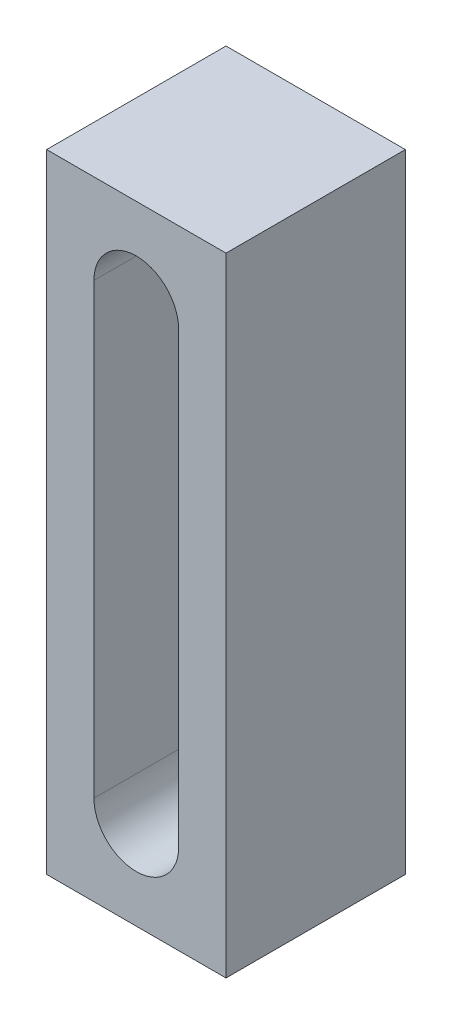
SolidWorks part; units mm, degrees
ref_plane "Front Plane" through (0, 0, 0) normal (0, 0, 1) x (1, 0, 0)
ref_plane "Top Plane" through (0, 0, 0) normal (0, 1, 0) x (1, 0, 0)
ref_plane "Right Plane" through (0, 0, 0) normal (1, 0, 0) x (0, 0, -1)
sketch "Sketch1" plane through (0, 0, 0) normal (0, 0, 1) x (1, 0, 0)
  line L0 (0, -7.9375) -> (0, 7.9375) construction
  line L1 (-1.5, -7.9375) -> (-1.5, 7.9375)
  line L2 (1.5, -7.9375) -> (1.5, 7.9375)
  line L4 (3.175, -11.1125) -> (-3.175, -11.1125)
  line L5 (3.175, -11.1125) -> (3.175, 11.1125)
  line L6 (3.175, 11.1125) -> (-3.175, 11.1125)
  line L7 (-3.175, -11.1125) -> (-3.175, 11.1125)
  line L8 (3.175, -11.1125) -> (-3.175, 11.1125) construction
  line L9 (3.175, 11.1125) -> (-3.175, -11.1125) construction
  arc A0 (-1.5, -7.9375) -> (1.5, -7.9375) centre (0, -7.9375) ccw
  arc A1 (1.5, 7.9375) -> (-1.5, 7.9375) centre (0, 7.9375) ccw
  point P2 (0, 0)
  point P7 (0, 0)
  dimension "D4" = 1.5
  dimension "D1" = 6.35
  dimension "D2" = 22.225
  dimension "D3" = 15.875
extrude "Boss-Extrude1" add sketch "Sketch1" along normal mid plane 6.35
